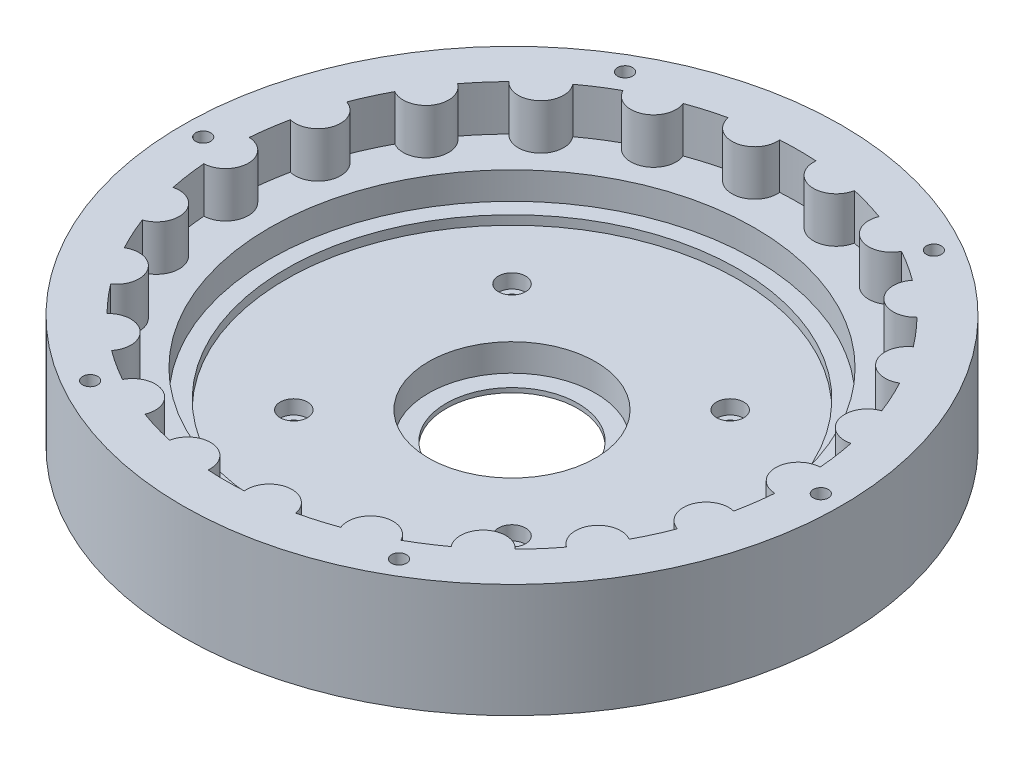
SolidWorks part; units mm, degrees
ref_plane "Front Plane" through (0, 0, 0) normal (0, 0, 1) x (1, 0, 0)
ref_plane "Top Plane" through (0, 0, 0) normal (0, 1, 0) x (1, 0, 0)
ref_plane "Right Plane" through (0, 0, 0) normal (1, 0, 0) x (0, 0, -1)
sketch "Sketch1" plane through (0, 0, 0) normal (0, 1, 0) x (1, 0, 0)
  line L0 (-58.7922, -0.6081) -> (57.2078, -0.6081) construction
  line L3 (-0.7922, -72.9097) -> (-0.7922, 67.4113) construction
  arc A0 (62.0094, 4.388) -> (60.8731, 12.2915) centre (-0.7922, -0.6081) ccw construction
  arc A1 (-63.5938, -5.6041) -> (-63.5938, 4.388) centre (-63.7922, -0.6081) ccw
  arc A2 (-62.4574, 12.2915) -> (-59.6423, 21.8789) centre (-61.2402, 17.1411) ccw
  arc A3 (-56.3253, 29.1421) -> (-50.9231, 37.548) centre (-53.7911, 33.4523) ccw
  arc A4 (-45.6942, 43.5825) -> (-38.1427, 50.1259) centre (-42.0484, 47.0042) ccw
  arc A5 (-31.4255, 54.4428) -> (-22.3363, 58.5937) centre (-26.9633, 56.6987) ccw
  arc A6 (-14.675, 60.8433) -> (-4.7846, 62.2653) centre (-9.758, 61.7507) ccw
  arc A7 (3.2002, 62.2653) -> (13.0906, 60.8433) centre (8.1737, 61.7507) ccw
  arc A8 (20.752, 58.5937) -> (29.8411, 54.4428) centre (25.379, 56.6987) ccw
  arc A9 (36.5584, 50.1259) -> (44.1099, 43.5825) centre (40.4641, 47.0042) ccw
  arc A10 (49.3388, 37.548) -> (54.741, 29.1421) centre (52.2068, 33.4523) ccw
  arc A11 (58.058, 21.8789) -> (60.8731, 12.2915) centre (59.6559, 17.1411) ccw
  arc A12 (62.0094, 4.388) -> (62.0094, -5.6041) centre (62.2078, -0.6081) ccw
  arc A13 (60.8731, -13.5076) -> (58.058, -23.095) centre (59.6559, -18.3572) ccw
  arc A14 (54.741, -30.3582) -> (49.3388, -38.7641) centre (52.2068, -34.6684) ccw
  arc A15 (44.1099, -44.7986) -> (36.5584, -51.3421) centre (40.4641, -48.2203) ccw
  arc A16 (29.8411, -55.659) -> (20.752, -59.8098) centre (25.379, -57.9149) ccw
  arc A17 (13.0906, -62.0594) -> (3.2002, -63.4814) centre (8.1737, -62.9668) ccw
  arc A18 (-4.7846, -63.4814) -> (-14.675, -62.0594) centre (-9.758, -62.9668) ccw
  arc A19 (-22.3363, -59.8098) -> (-31.4255, -55.659) centre (-26.9633, -57.9149) ccw
  arc A20 (-38.1427, -51.3421) -> (-45.6942, -44.7986) centre (-42.0484, -48.2203) ccw
  arc A21 (-50.9231, -38.7641) -> (-56.3253, -30.3582) centre (-53.7911, -34.6684) ccw
  arc A22 (-59.6423, -23.095) -> (-62.4574, -13.5076) centre (-61.2402, -18.3572) ccw
  circle A36 centre (-0.7922, -0.6081) radius 53.375
  circle A38 centre (-0.7922, -0.6081) radius 72.5
  arc A39 (62.0094, 4.388) -> (60.8731, 12.2915) centre (-0.7922, -0.6081) ccw
  arc A40 (58.058, 21.8789) -> (54.741, 29.1421) centre (-0.7922, -0.6081) ccw
  arc A41 (58.058, 21.8789) -> (62.0094, -5.6041) centre (-0.7922, -0.6081) ccw construction
  arc A42 (60.8731, -13.5076) -> (62.0094, -5.6041) centre (-0.7922, -0.6081) ccw
  arc A43 (54.741, -30.3582) -> (58.058, -23.095) centre (-0.7922, -0.6081) ccw
  arc A44 (44.1099, -44.7986) -> (49.3388, -38.7641) centre (-0.7922, -0.6081) ccw
  arc A45 (29.8411, -55.659) -> (36.5584, -51.3421) centre (-0.7922, -0.6081) ccw
  arc A46 (13.0906, -62.0594) -> (20.752, -59.8098) centre (-0.7922, -0.6081) ccw
  arc A47 (-4.7846, -63.4814) -> (3.2002, -63.4814) centre (-0.7922, -0.6081) ccw
  arc A48 (-22.3363, -59.8098) -> (-14.675, -62.0594) centre (-0.7922, -0.6081) ccw
  arc A49 (-38.1427, -51.3421) -> (-31.4255, -55.659) centre (-0.7922, -0.6081) ccw
  arc A50 (-50.9231, -38.7641) -> (-45.6942, -44.7986) centre (-0.7922, -0.6081) ccw
  arc A51 (-59.6423, -23.095) -> (-56.3253, -30.3582) centre (-0.7922, -0.6081) ccw
  arc A52 (-63.5938, -5.6041) -> (-62.4574, -13.5076) centre (-0.7922, -0.6081) ccw
  arc A53 (-62.4574, 12.2915) -> (-63.5938, 4.388) centre (-0.7922, -0.6081) ccw
  arc A54 (-56.3253, 29.1421) -> (-59.6423, 21.8789) centre (-0.7922, -0.6081) ccw
  arc A55 (-45.6942, 43.5825) -> (-50.9231, 37.548) centre (-0.7922, -0.6081) ccw
  arc A56 (-31.4255, 54.4428) -> (-38.1427, 50.1259) centre (-0.7922, -0.6081) ccw
  arc A57 (-14.675, 60.8433) -> (-22.3363, 58.5937) centre (-0.7922, -0.6081) ccw
  arc A58 (3.2002, 62.2653) -> (-4.7846, 62.2653) centre (-0.7922, -0.6081) ccw
  arc A59 (20.752, 58.5937) -> (13.0906, 60.8433) centre (-0.7922, -0.6081) ccw
  arc A60 (36.5584, 50.1259) -> (29.8411, 54.4428) centre (-0.7922, -0.6081) ccw
  arc A61 (49.3388, 37.548) -> (44.1099, 43.5825) centre (-0.7922, -0.6081) ccw
  circle A62 centre (-0.7922, -0.6081) radius 18.375
  circle A72 centre (-0.7922, -0.6081) radius 49.75
  circle A73 centre (-0.7922, -0.6081) radius 14.5
  circle A74 centre (-68.73, -0.6081) radius 1.65
  circle A75 centre (-68.73, -0.6081) radius 3
  circle A76 centre (-34.7611, 58.2279) radius 1.65
  circle A77 centre (-34.7611, 58.2279) radius 3
  circle A78 centre (33.1768, 58.2279) radius 1.65
  circle A79 centre (33.1768, 58.2279) radius 3
  circle A80 centre (67.1457, -0.6081) radius 1.65
  circle A81 centre (67.1457, -0.6081) radius 3
  circle A82 centre (33.1768, -59.444) radius 1.65
  circle A83 centre (33.1768, -59.444) radius 3
  circle A84 centre (-34.7611, -59.444) radius 1.65
  circle A85 centre (-34.7611, -59.444) radius 3
  circle A86 centre (-24.7922, 23.3919) radius 3
  circle A87 centre (-24.7922, 23.3919) radius 1.65
  circle A88 centre (23.2078, 23.3919) radius 1.65
  circle A89 centre (23.2078, 23.3919) radius 3
  circle A90 centre (23.2078, -24.6081) radius 1.65
  circle A91 centre (23.2078, -24.6081) radius 3
  circle A92 centre (-24.7922, -24.6081) radius 1.65
  circle A93 centre (-24.7922, -24.6081) radius 3
  dimension "D2" = 126
  dimension "D3" = 10
  dimension "D4" = 145
  dimension "D5" = 36.75
  dimension "D6" = 99.5
  dimension "D7" = 106.75
  dimension "D12" = 29
  dimension "D13" = 3.3
  dimension "D14" = 6
  dimension "D18" = 6
  dimension "D19" = 3.3
  dimension "D16" = 24
  dimension "D17" = 24
  dimension "D15" = 6
  dimension "D20" = 4
extrude "Boss-Extrude1" add sketch "Sketch1" along normal blind 25 contours A38 | A53 A1 A52 A22 A51 A21 A50 A20 A49 A19 A48 A18 A47 A17 A46 A16 A45 A15 A44 A14 A43 A13 A42 A12 A39 A11 A40 A10 A61 A9 A60 A8 A59 A7 A58 A6 A57 A5 A56 A4 A55 A3 A54 A2
extrude "Boss-Extrude2" add sketch "Sketch1<4>" along normal blind 1 contours A38 | A73
sketch "Sketch1<4>" plane through (0, 0, 0) normal (0, 1, 0) x (1, 0, 0) same geometry as "Sketch1"
extrude "Boss-Extrude3" add sketch "Sketch1<5>" along normal blind 7 contours A38 | A62
sketch "Sketch1<5>" plane through (0, 0, 0) normal (0, 1, 0) x (1, 0, 0) same geometry as "Sketch1"
extrude "Boss-Extrude5" add sketch "Sketch1<8>" along normal blind 9 contours A38 | A72
sketch "Sketch1<8>" plane through (0, 0, 0) normal (0, 1, 0) x (1, 0, 0) same geometry as "Sketch1"
extrude "Boss-Extrude6" add sketch "Sketch1<10>" along normal blind 15 contours A38 | A36
sketch "Sketch1<10>" plane through (0, 0, 0) normal (0, 1, 0) x (1, 0, 0) same geometry as "Sketch1"
extrude "Cut-Extrude1" cut sketch "Sketch1<11>" along normal through all contours A74 | A76 | A78 | A80 | A82 | A84
sketch "Sketch1<11>" plane through (0, 0, 0) normal (0, 1, 0) x (1, 0, 0) same geometry as "Sketch1"
extrude "Cut-Extrude2" cut sketch "Sketch1<12>" along normal blind 8 contours A75 | A81 | A83 | A85 | A77 | A79
sketch "Sketch1<12>" plane through (0, 0, 0) normal (0, 1, 0) x (1, 0, 0) same geometry as "Sketch1"
extrude "Cut-Extrude3" cut sketch "Sketch1<15>" along normal blind 20 contours A87 | A88 | A90 | A92
sketch "Sketch1<15>" plane through (0, 0, 0) normal (0, 1, 0) x (1, 0, 0) same geometry as "Sketch1"
extrude "Cut-Extrude4" cut sketch "Sketch1<16>" against normal blind 3.1 from surface contours A86 | A93 | A89 | A91 starting at face at (-24.7922, 7, 26.2581)
sketch "Sketch1<16>" plane through (0, 0, 0) normal (0, 1, 0) x (1, 0, 0) same geometry as "Sketch1"
equation "\"R\"= 63mm"
equation "\"E\"= 2mm"
equation "\"Rr\"= 5"
equation "\"N\"= 22"
equation "\"M5\"= 5"
equation "\"SMALL_BEARING_DEPTH\"= 6MM"
